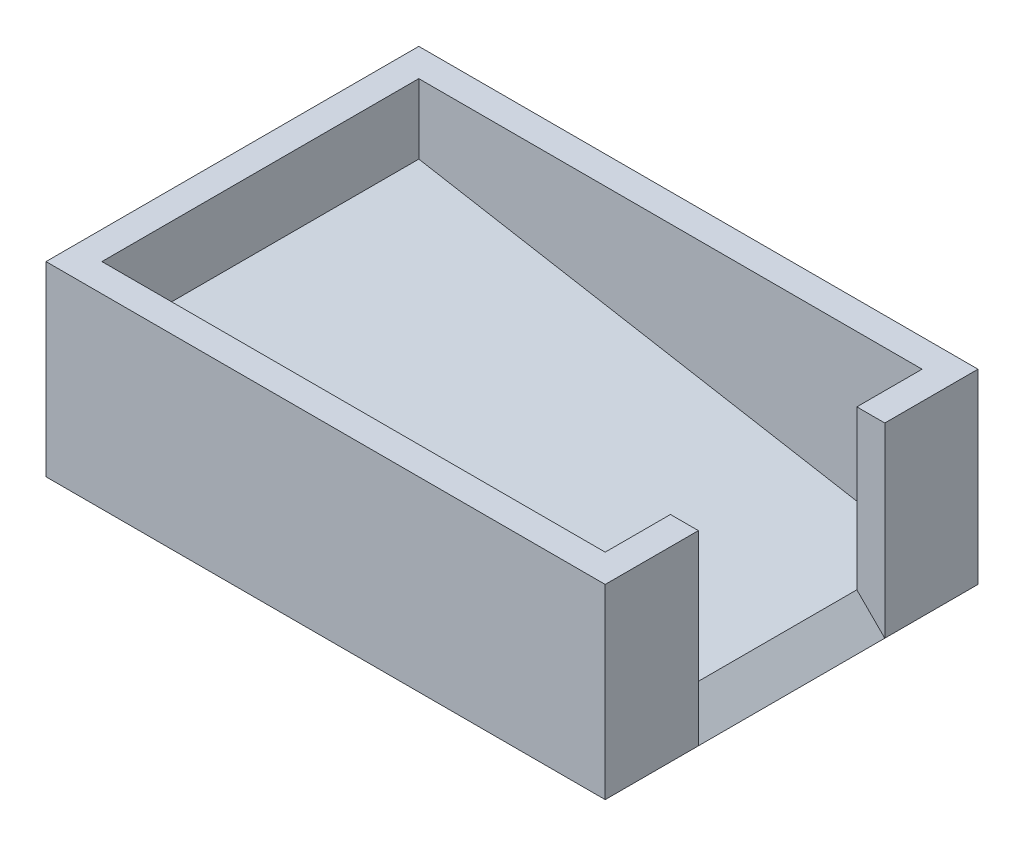
SolidWorks part; units mm, degrees
ref_plane "Front Plane" through (0, 0, 0) normal (0, 0, 1) x (1, 0, 0)
ref_plane "Top Plane" through (0, 0, 0) normal (0, 1, 0) x (1, 0, 0)
ref_plane "Right Plane" through (0, 0, 0) normal (1, 0, 0) x (0, 0, -1)
sketch "Sketch1" plane through (0, 0, 0) normal (0, 1, 0) x (1, 0, 0)
  line L1 (-30, -20) -> (30, -20)
  line L2 (-30, -20) -> (-30, 20)
  line L3 (-30, 20) -> (30, 20)
  line L4 (30, -20) -> (30, 20)
  line L5 (-30, -20) -> (30, 20) construction
  line L6 (-30, 20) -> (30, -20) construction
  line L7 (-9.5, -7.5) -> (9.5, -7.5)
  line L8 (-9.5, -7.5) -> (-9.5, 7.5)
  line L9 (-9.5, 7.5) -> (9.5, 7.5)
  line L10 (9.5, -7.5) -> (9.5, 7.5)
  line L11 (-9.5, -7.5) -> (9.5, 7.5) construction
  line L12 (-9.5, 7.5) -> (9.5, -7.5) construction
  point P0 (0, 0)
  point P6 (0, 0)
  dimension "D1" = 40
  dimension "D2" = 60
  dimension "D3" = 15
  dimension "D4" = 19
extrude "Boss-Extrude1" add sketch "Sketch1" along normal blind 20 contours L1 L4 L3 L2 L10 L7 L8 L9 | L7 L10 L9 L8 region at (-29.2789, 0, 0) region at (0, 0, 0)
shell "Shell2" thickness 3 removed face at (0, 20, 0)
extrude "Boss-Extrude2" add sketch "Sketch1<3>" against normal blind 3 contours L7 L10 L9 L8 region at (0, 0, 0)
sketch "Sketch1<3>" plane through (0, 0, 0) normal (0, 1, 0) x (1, 0, 0) same geometry as "Sketch1"
sketch "Sketch2" plane through (30, 0, 0) normal (1, 0, 0) x (0, 0, -1)
  line L0 (-20, 20) -> (20, 20) construction
  line L1 (-10, 20) -> (10, 20)
  line L2 (-10, 20) -> (-10, 3)
  line L3 (-10, 3) -> (10, 3)
  line L4 (10, 20) -> (10, 3)
  point P6 (0, 0)
  point P7 (0, 3)
  dimension "D1" = 20
  dimension "D2" = 17
extrude "Cut-Extrude1" cut sketch "Sketch2" against normal blind 3
chamfer "Chamfer1" distance 3 angle 45 1 edges at (30, 3, 0)
sketch "Sketch3" plane through (0, 0, -17) normal (0, 0, 1) x (1, 0, 0)
  line L0 (-27, 3) -> (27, 3)
  line L1 (27, 3) -> (-27, 12.5217)
  line L2 (-27, 20) -> (-27, 3) construction
  line L3 (-27, 12.5217) -> (-27, 3)
  dimension "D1" = 10
extrude "Boss-Extrude3" add sketch "Sketch3" along normal up to next
